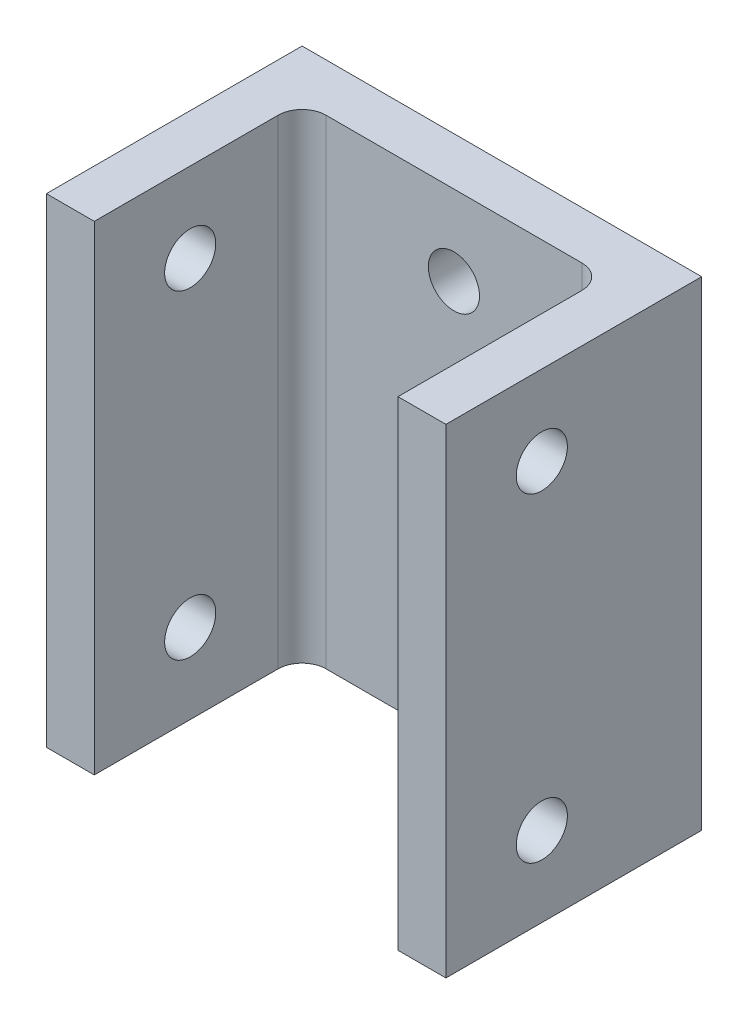
SolidWorks part; units mm, degrees
ref_plane "前视基准面" through (0, 0, 0) normal (0, 0, 1) x (1, 0, 0)
ref_plane "上视基准面" through (0, 0, 0) normal (0, 1, 0) x (1, 0, 0)
ref_plane "右视基准面" through (0, 0, 0) normal (1, 0, 0) x (0, 0, -1)
sketch "草图1" plane through (0, 0, 0) normal (0, 0, 1) x (1, 0, 0)
  line L1 (253.9883, -73.1089) -> (278.9883, -73.1089)
  line L2 (253.9883, -73.1089) -> (253.9883, -43.1089)
  line L3 (253.9883, -43.1089) -> (278.9883, -43.1089)
  line L4 (278.9883, -73.1089) -> (278.9883, -43.1089)
  dimension "D1" = 25
  dimension "D2" = 30
extrude "凸台-拉伸1" add sketch "草图1" along normal blind 3
sketch "草图2" plane through (0, 0, 3) normal (0, 0, 1) x (1, 0, 0)
  line L0 (253.9883, -43.1089) -> (253.9883, -73.1089) construction
  line L1 (253.9883, -73.1089) -> (256.9883, -73.1089)
  line L2 (253.9883, -73.1089) -> (253.9883, -43.1089)
  line L3 (253.9883, -43.1089) -> (256.9883, -43.1089)
  line L4 (256.9883, -73.1089) -> (256.9883, -43.1089)
  line L5 (278.9883, -43.1089) -> (253.9883, -43.1089) construction
  line L6 (253.9883, -73.1089) -> (278.9883, -73.1089) construction
  line L7 (278.9883, -43.1089) -> (275.9883, -43.1089)
  line L8 (278.9883, -43.1089) -> (278.9883, -73.1089)
  line L9 (278.9883, -73.1089) -> (275.9883, -73.1089)
  line L10 (275.9883, -43.1089) -> (275.9883, -73.1089)
  point P15 (253.9883, -73.1089)
  dimension "D1" = 3
  dimension "D2" = 3
extrude "凸台-拉伸2" add sketch "草图2" along normal blind 15
sketch "草图3" plane through (253.9883, 0, 0) normal (-1, 0, 0) x (0, 0, 1)
  line L0 (18, -73.1089) -> (0, -73.1089) construction
  line L1 (18, -43.1089) -> (18, -73.1089) construction
  circle A0 centre (10, -48.1089) radius 1.6
  circle A1 centre (10, -68.1089) radius 1.6
  dimension "D1" = 3.2
  dimension "D2" = 3.2
  dimension "D3" = 20
  dimension "D4" = 5
  dimension "D5" = 8
  dimension "D6" = 8
extrude "切除-拉伸1" cut sketch "草图3" against normal blind 30
sketch "草图4" plane through (0, 0, 3) normal (0, 0, 1) x (1, 0, 0)
  line L1 (256.9883, -73.1089) -> (275.9883, -73.1089) construction
  line L2 (275.9883, -43.1089) -> (275.9883, -73.1089) construction
  circle A0 centre (266.4883, -48.1089) radius 1.6
  circle A1 centre (266.4883, -68.1089) radius 1.6
  dimension "D1" = 3.2
  dimension "D2" = 3.2
  dimension "D4" = 5
  dimension "D6" = 9.5
  dimension "D3" = 20
  dimension "D5" = 9.5
extrude "切除-拉伸2" cut sketch "草图4" against normal blind 30
sketch "草图5" plane through (253.9883, 0, 0) normal (-1, 0, 0) x (0, 0, 1)
  line L0 (18, -43.1089) -> (0, -43.1089) construction
  line L1 (16, -43.1089) -> (25.9736, -43.1089)
  line L2 (16, -43.1089) -> (16, -74.7139)
  line L3 (16, -74.7139) -> (25.9736, -74.7139)
  line L4 (25.9736, -43.1089) -> (25.9736, -74.7139)
  line L5 (16, -12.1089) -> (16, -204.1089) construction
extrude "切除-拉伸3" cut sketch "草图5" against normal blind 29
fillet "圆角1" radius 1.5 2 edges at (256.9883, -58.1089, 3) (275.9883, -58.1089, 3)
